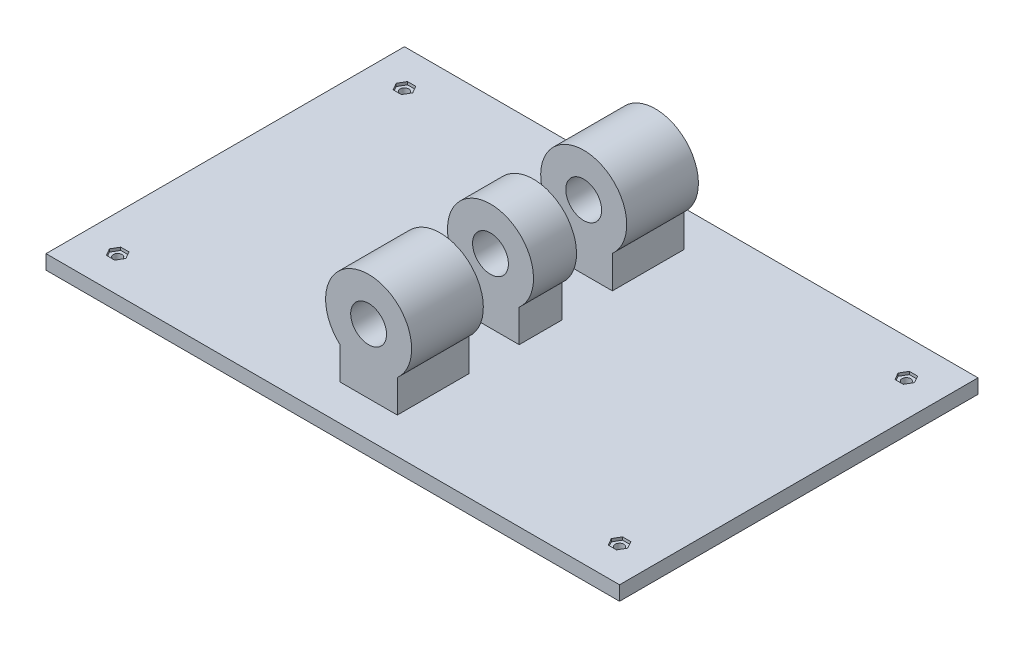
SolidWorks part; units mm, degrees
ref_plane "Front Plane" through (0, 0, 0) normal (0, 0, 1) x (1, 0, 0)
ref_plane "Top Plane" through (0, 0, 0) normal (0, 1, 0) x (1, 0, 0)
ref_plane "Right Plane" through (0, 0, 0) normal (1, 0, 0) x (0, 0, -1)
sketch "Sketch1" plane through (0, 0, 0) normal (0, 1, 0) x (1, 0, 0)
  line L0 (200, 250) -> (200, 0) construction
  line L1 (0, 0) -> (400, 0)
  line L2 (0, 0) -> (0, 250)
  line L3 (0, 250) -> (400, 250)
  line L4 (400, 0) -> (400, 250)
  line L5 (25, 225) -> (375, 225) construction
  line L6 (375, 25) -> (375, 225) construction
  line L7 (25, 25) -> (375, 25) construction
  line L8 (25, 25) -> (25, 225) construction
  line L9 (200, 125) -> (25, 125) construction
  line L10 (30.7735, 225) -> (27.8868, 230) construction
  line L11 (27.8868, 230) -> (22.1132, 230) construction
  line L12 (22.1132, 230) -> (19.2265, 225) construction
  line L13 (19.2265, 225) -> (22.1132, 220) construction
  line L14 (22.1132, 220) -> (27.8868, 220) construction
  line L15 (27.8868, 220) -> (30.7735, 225) construction
  line L16 (27.8868, 30) -> (30.7735, 25) construction
  line L17 (22.1132, 30) -> (27.8868, 30) construction
  line L18 (19.2265, 25) -> (22.1132, 30) construction
  line L19 (22.1132, 20) -> (19.2265, 25) construction
  line L20 (27.8868, 20) -> (22.1132, 20) construction
  line L21 (30.7735, 25) -> (27.8868, 20) construction
  line L22 (377.8868, 30) -> (372.1132, 30) construction
  line L23 (380.7735, 25) -> (377.8868, 30) construction
  line L24 (377.8868, 20) -> (380.7735, 25) construction
  line L25 (372.1132, 20) -> (377.8868, 20) construction
  line L26 (369.2265, 25) -> (372.1132, 20) construction
  line L27 (372.1132, 30) -> (369.2265, 25) construction
  line L28 (372.1132, 220) -> (369.2265, 225) construction
  line L29 (377.8868, 220) -> (372.1132, 220) construction
  line L30 (380.7735, 225) -> (377.8868, 220) construction
  line L31 (377.8868, 230) -> (380.7735, 225) construction
  line L32 (372.1132, 230) -> (377.8868, 230) construction
  line L33 (369.2265, 225) -> (372.1132, 230) construction
  circle A0 centre (25, 225) radius 3
  circle A1 centre (25, 225) radius 5 construction
  circle A2 centre (25, 25) radius 3
  circle A3 centre (375, 25) radius 3
  circle A4 centre (375, 225) radius 3
  dimension "D3" = 6
  dimension "D1" = 400
  dimension "D2" = 250
  dimension "D5" = 10
  dimension "D4" = 25
extrude "Boss-Extrude1" add sketch "Sketch1" along normal blind 10
sketch "Sketch6" plane through (0, 10, 0) normal (0, 1, 0) x (1, 0, 0)
  line L0 (200, 250) -> (200, 0) construction
  line L1 (30.7735, 225) -> (27.8868, 230)
  line L2 (27.8868, 230) -> (22.1132, 230)
  line L3 (22.1132, 230) -> (19.2265, 225)
  line L4 (19.2265, 225) -> (22.1132, 220)
  line L5 (22.1132, 220) -> (27.8868, 220)
  line L6 (27.8868, 220) -> (30.7735, 225)
  line L7 (400, 250) -> (0, 250) construction
  line L8 (0, 0) -> (400, 0) construction
  line L9 (200, 125) -> (0, 125) construction
  line L10 (0, 250) -> (0, 0) construction
  line L11 (27.8868, 30) -> (30.7735, 25)
  line L12 (22.1132, 30) -> (27.8868, 30)
  line L13 (19.2265, 25) -> (22.1132, 30)
  line L14 (22.1132, 20) -> (19.2265, 25)
  line L15 (27.8868, 20) -> (22.1132, 20)
  line L16 (30.7735, 25) -> (27.8868, 20)
  line L17 (377.8868, 30) -> (372.1132, 30)
  line L18 (380.7735, 25) -> (377.8868, 30)
  line L19 (377.8868, 20) -> (380.7735, 25)
  line L20 (372.1132, 20) -> (377.8868, 20)
  line L21 (369.2265, 25) -> (372.1132, 20)
  line L22 (372.1132, 30) -> (369.2265, 25)
  line L23 (372.1132, 220) -> (369.2265, 225)
  line L24 (377.8868, 220) -> (372.1132, 220)
  line L25 (380.7735, 225) -> (377.8868, 220)
  line L26 (377.8868, 230) -> (380.7735, 225)
  line L27 (372.1132, 230) -> (377.8868, 230)
  line L28 (369.2265, 225) -> (372.1132, 230)
  circle A0 centre (25, 225) radius 5 construction
  dimension "D1" = 10
extrude "Cut-Extrude1" cut sketch "Sketch6" against normal blind 2
sketch "Sketch7" plane through (0, 10, 0) normal (0, 1, 0) x (1, 0, 0)
  line L0 (0, 0) -> (400, 0) construction
  line L1 (180, 25) -> (220, 25)
  line L2 (180, 25) -> (180, 75)
  line L3 (180, 75) -> (220, 75)
  line L4 (220, 25) -> (220, 75)
  line L5 (200, 0) -> (200, 250) construction
  line L6 (400, 250) -> (0, 250) construction
  line L8 (180, 110) -> (220, 110)
  line L9 (180, 110) -> (180, 140)
  line L10 (180, 140) -> (220, 140)
  line L11 (220, 110) -> (220, 140)
  point P11 (200, 75)
  point P12 (200, 125)
  point P16 (180, 125)
  point P17 (200, 110)
  dimension "D1" = 40
  dimension "D2" = 50
  dimension "D3" = 50
  dimension "D4" = 30
extrude "Boss-Extrude2" add sketch "Sketch7" along normal blind 22.6393
sketch "Sketch11" plane through (0, 0, -25) normal (0, 0, 1) x (1, 0, 0)
  circle A0 centre (200, 55) radius 30
  circle A1 centre (200, 55) radius 12.5
  dimension "D1" = 60
  dimension "D2" = 25
extrude "Boss-Extrude3" add sketch "Sketch11" against normal up to surface (115 mm away) up to face at (200, 21.3197, -140)
ref_plane "Plane1" through (0, 0, -125) normal (0, 0, 1) x (1, 0, 0)
sketch "Sketch12" plane through (400, 0, 0) normal (1, 0, 0) x (0, 0, -1)
  line L0 (140, 85) -> (25, 85) construction
  line L1 (75, 10) -> (110, 10)
  line L2 (75, 10) -> (75, 85)
  line L3 (75, 85) -> (110, 85)
  line L4 (110, 10) -> (110, 85)
  line L5 (110, 32.6393) -> (110, 10) construction
extrude "Cut-Extrude2" cut sketch "Sketch12" against normal through all
mirror "Mirror4" about plane through (0, 0, -125) normal (0, 0, 1) of "Cut-Extrude2", "Boss-Extrude3", "Boss-Extrude2"
equation "\"joint_width\"=4"
equation "\"D2@Sketch7\"=\"short_base_length\"/5"
equation "\"short_base_length\"=25"
equation "\"D2@Sketch1\"=\"short_base_length\""
equation "\"outer_diam_main_joint\"=6"
equation "\"D1@Sketch11\"=\"outer_diam_main_joint\""
equation "\"D1@Sketch7\"=\"outer_diam_main_joint\"-2"
equation "\"D1@Boss-Extrude2\"=(\"outer_diam_main_joint\"/2)+1.5cm-sqr((\"outer_diam_main_joint\"/2)^2-((\"outer_diam_main_joint\"-2)/2)^2)"
